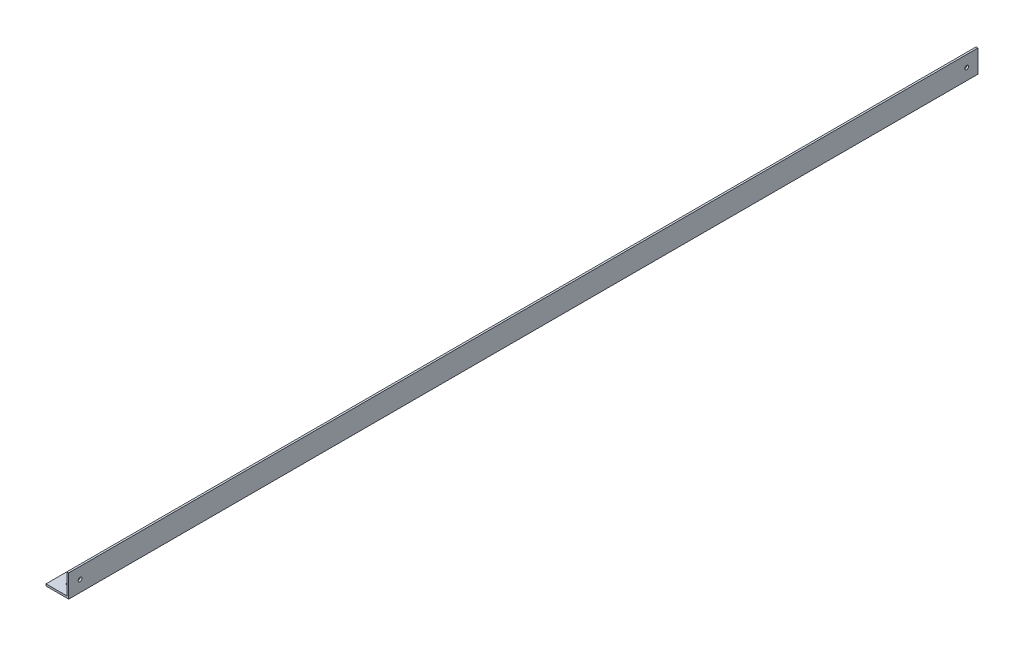
SolidWorks part; units mm, degrees
material "1060 Alloy"
ref_plane "Front Plane" through (0, 0, 0) normal (0, 0, 1) x (1, 0, 0)
ref_plane "Top Plane" through (0, 0, 0) normal (0, 1, 0) x (1, 0, 0)
ref_plane "Right Plane" through (0, 0, 0) normal (1, 0, 0) x (0, 0, -1)
sketch "Sketch1" plane through (0, 0, 0) normal (0, 0, 1) x (1, 0, 0)
  line L0 (0, 0) -> (0, 19.05)
  line L1 (0, 0) -> (19.05, 0)
  line L2 (0, 19.05) -> (1.5875, 19.05)
  line L3 (19.05, 0) -> (19.05, 1.5875)
  line L4 (19.05, 1.5875) -> (1.5875, 1.5875)
  line L5 (1.5875, 1.5875) -> (1.5875, 19.05)
  dimension "D1" = 19.05
  dimension "D2" = 19.05
  dimension "D3" = 1.5875
  dimension "D4" = 1.5875
extrude "Boss-Extrude1" add sketch "Sketch1" against normal blind 762
ref_axis "Axis1" through (0, 0, 0) along (0.7071, 0.7071, 0)
ref_plane "Plane1" through (0, 0, 0) normal (-0.7071, 0.7071, 0) x (0.7071, 0.7071, 0)
sketch "Sketch2" plane through (0, 1.5875, 0) normal (0, 1, 0) x (1, 0, 0)
  line L0 (1.5875, 762) -> (9.525, 762)
  line L1 (19.05, 0) -> (1.5875, 0) construction
  line L2 (9.525, 9.525) -> (9.525, 50009.525) construction
  line L3 (19.05, 762) -> (1.5875, 762) construction
  line L4 (9.525, 9.525) -> (1.5875, 9.525) construction
  line L5 (1.5875, 762) -> (1.5875, 0) construction
  line L6 (9.525, 762) -> (9.525, 752.475) construction
  circle A0 centre (9.525, 9.525) radius 1.5875
  circle A5 centre (9.525, 752.475) radius 1.5875
  circle A6 centre (9.525, 76.2) radius 3.175
  circle A7 centre (9.525, 703.58) radius 3.175
  dimension "D2" = 6.35
  dimension "D3" = 9.525
  dimension "D4" = 3.175
  dimension "D6" = 6.35
  dimension "D8" = 3.175
  dimension "D5" = 76.2
  dimension "D7" = 58.42
  dimension "D9" = 7.9375
  dimension "D10" = 9.525
extrude "Cut-Extrude2" cut sketch "Sketch2" against normal blind 2.794 contours A0 | A5 | A6 | A7
sketch "Sketch4" plane through (1.5875, 0, 0) normal (1, 0, 0) x (0, 0, -1)
  line L0 (752.475, 9.525) -> (762, 9.525) construction
  line L1 (0, 19.05) -> (0, 0) construction
  line L2 (0, 9.525) -> (50000, 9.525) construction
  line L3 (0, 1.5875) -> (0, 19.05) construction
  line L4 (0, 1.5875) -> (0, 9.525)
  line L5 (762, 1.5875) -> (762, 19.05) construction
  circle A0 centre (9.525, 9.525) radius 1.5875
  circle A2 centre (752.475, 9.525) radius 1.5875
  dimension "D1" = 9.525
  dimension "D2" = 3.175
  dimension "D3" = 9.525
  dimension "D4" = 3.175
  dimension "D12" = 7.9375
extrude "Cut-Extrude3" cut sketch "Sketch4" against normal blind 8.89 contours A2 | A0
mirror "Mirror1" about plane through (19.05, 0, -762) normal (1, 0, 0) of "Cut-Extrude3", "Boss-Extrude1", "Cut-Extrude2"
sketch "Sketch5" plane through (0, 0, 0) normal (0, 0, 1) x (1, 0, 0)
  line L0 (0, 0) -> (38.1, 0) construction
  line L1 (0, 19.05) -> (19.05, 19.05)
  line L2 (0, 19.05) -> (0, 0)
  line L3 (0, 0) -> (19.05, 0)
  line L4 (19.05, 19.05) -> (19.05, 0)
extrude "Cut-Extrude4" cut sketch "Sketch5" against normal through all
